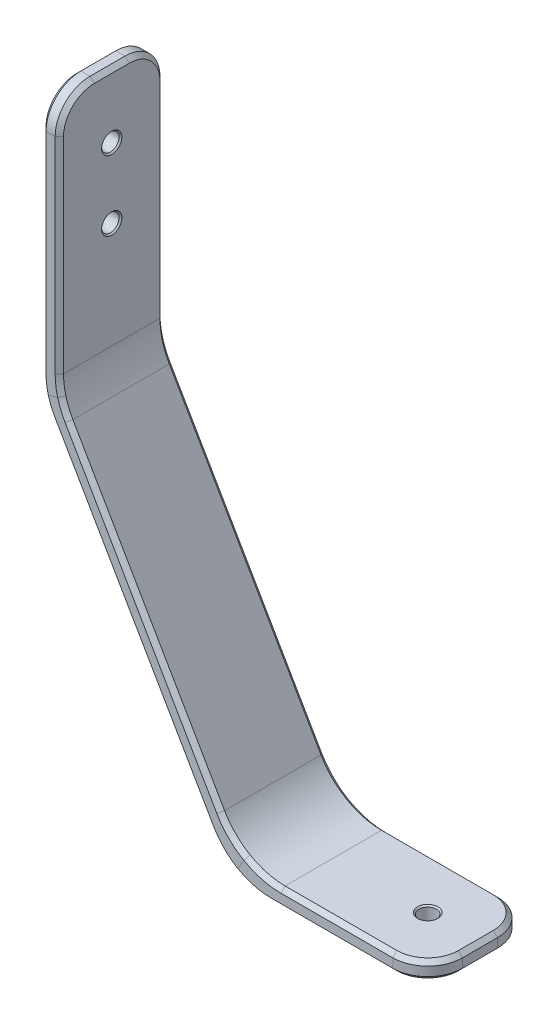
SolidWorks part; units mm, degrees
ref_plane "Front Plane" through (0, 0, 0) normal (0, 0, 1) x (1, 0, 0)
ref_plane "Top Plane" through (0, 0, 0) normal (0, 1, 0) x (1, 0, 0)
ref_plane "Right Plane" through (0, 0, 0) normal (1, 0, 0) x (0, 0, -1)
sketch "Sketch1" plane through (0, 0, 0) normal (0, 0, 1) x (1, 0, 0)
  line L0 (0, 0) -> (0, -47.5145)
  line L1 (0, -47.5145) -> (33.6108, -105.7302)
  line L2 (33.6108, -105.7302) -> (68.5358, -105.7302)
  dimension "D1" = 47.5145
  dimension "D3" = 150
  dimension "D4" = 120
  dimension "D5" = 34.925
  dimension "D2" = 58.2157
sketch "Sketch2" plane through (0, 0, 0) normal (0, 1, 0) x (1, 0, 0)
  line L1 (-1.5875, -9.525) -> (1.5875, -9.525)
  line L2 (-1.5875, -9.525) -> (-1.5875, 9.525)
  line L3 (-1.5875, 9.525) -> (1.5875, 9.525)
  line L4 (1.5875, -9.525) -> (1.5875, 9.525)
  line L5 (-1.5875, -9.525) -> (1.5875, 9.525) construction
  line L6 (-1.5875, 9.525) -> (1.5875, -9.525) construction
  point P0 (0, 0)
  dimension "D1" = 3.175
  dimension "D2" = 19.05
sweep "Sweep1" add profiles "Sketch2" path "Sketch1"
hole_wizard "1/8 (0.125) Diameter Hole1" positions "Sketch3" profile "Sketch4" hole size "1/8" standard "ANSI Inch" end condition through all
sketch "Sketch3" plane through (1.5875, 0, 0) normal (1, 0, 0) x (0, 0, -1)
  line L4 (0, 0) -> (0, -11.6936) construction
  point P0 (0, -11.6936)
  point P2 (0, -24.3936)
  dimension "D1" = 12.7
  dimension "D2" = 11.6936
sketch "Sketch4" plane through (1.5875, -11.6936, 0) normal (0, 1, 0) x (0, 0, -1)
  line L0 (0, 0) -> (0, 3.175)
  line L1 (0, 3.175) -> (1.5875, 3.175)
  line L2 (1.5875, 3.175) -> (1.5875, 0)
  line L5 (1.5875, 0) -> (0, 0)
  line L11 (0, -6.35) -> (0, 107.95) construction
  dimension "Thru Hole Dia." = 3.175
  dimension "Thru Hole Depth" = 3.175
hole_wizard "1/8 (0.125) Diameter Hole2" positions "Sketch5" profile "Sketch6" hole size "1/8" standard "ANSI Inch" end condition through all
sketch "Sketch5" plane through (0, -104.1427, 0) normal (0, 1, 0) x (1, 0, 0)
  line L0 (68.5358, -9.525) -> (68.5358, 9.525) construction
  point P0 (59.0108, 0)
  dimension "D1" = 9.525
sketch "Sketch6" plane through (59.0108, -104.1427, 0) normal (1, 0, 0) x (0, 0, 1)
  line L0 (0, 0) -> (0, 3.175)
  line L1 (0, 3.175) -> (1.5875, 3.175)
  line L2 (1.5875, 3.175) -> (1.5875, 0)
  line L5 (1.5875, 0) -> (0, 0)
  line L11 (0, -6.35) -> (0, 107.95) construction
  dimension "Thru Hole Dia." = 3.175
  dimension "Thru Hole Depth" = 3.175
fillet "Fillet1" radius 12.7 4 edges at (-1.5875, -47.9399, 0) (1.5875, -47.0892, 0) (32.6943, -107.3177, 0) (34.5274, -104.1427, 0)
fillet "Fillet2" radius 6.35 4 edges at (68.5358, -105.7302, -9.525) (68.5358, -105.7302, 9.525) (0, 0, -9.525) (0, 0, 9.525)
chamfer "Chamfer3" distance 0.762 angle 45 40 edges at (14.571, -75.9273, -9.525) (-0.6208, -49.397, -9.525) (31.0464, -103.598, -9.525) (-1.4788, -46.1946, -9.525) (36.7396, -106.885, -9.525) (-1.5875, -25.4435, -9.525) (51.1062, -107.3177, -9.525) (-1.5875, -1.8599, -7.6651) (66.676, -107.3177, -7.6651) (-1.5875, 0, 0) (68.5358, -107.3177, 0) (-1.5875, -1.8599, 7.6651) (66.676, -107.3177, 7.6651) (-1.5875, -25.4435, 9.525) (51.1062, -107.3177, 9.525) (-1.4788, -46.1946, 9.525) (36.7396, -106.885, 9.525) (-0.6208, -49.397, 9.525) (31.0464, -103.598, 9.525) (14.571, -75.9273, 9.525) (17.0751, -73.9145, -9.525) (2.5542, -48.5463, -9.525) (32.8795, -100.423, -9.525) (1.6962, -45.3439, -9.525) (38.5727, -103.71, -9.525) (1.5875, -25.0181, -9.525) (52.0228, -104.1427, -9.525) (1.5875, -1.8599, -7.6651) (66.676, -104.1427, -7.6651) (1.5875, 0, 0) (68.5358, -104.1427, 0) (1.5875, -1.8599, 7.6651) (66.676, -104.1427, 7.6651) (1.5875, -25.0181, 9.525) (52.0228, -104.1427, 9.525) (1.6962, -45.3439, 9.525) (38.5727, -103.71, 9.525) (2.5542, -48.5463, 9.525) (32.8795, -100.423, 9.525) (17.0751, -73.9145, 9.525)
chamfer "Chamfer2" distance 0.254 angle 45 6 edges at (1.5875, -24.3936, -1.5875) (-1.5875, -24.3936, -1.5875) (1.5875, -11.6936, -1.5875) (-1.5875, -11.6936, -1.5875) (59.0108, -104.1427, 1.5875) (59.0108, -107.3177, 1.5875)
equation "\"D2@Sketch1\"=2.59807621 - 0.3069935 + 0.0008725"
equation "\"D1@Sketch1\"=1.25+0.1875+0.433151"
